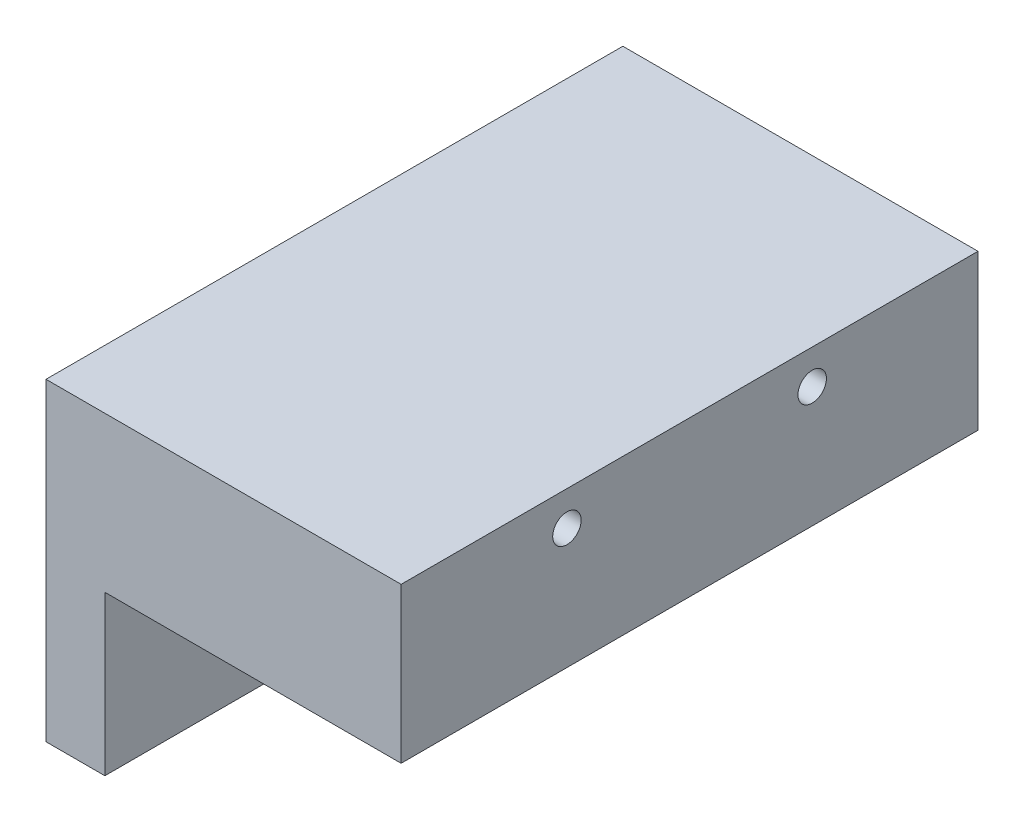
SolidWorks part; units mm, degrees
ref_plane "Front Plane" through (0, 0, 0) normal (1, 0, 0) x (0, 1, 0)
ref_plane "Top Plane" through (0, 0, 0) normal (0, 0, 1) x (0, 1, 0)
ref_plane "Right Plane" through (0, 0, 0) normal (0, 1, 0) x (-1, 0, 0)
sketch "Sketch1" plane through (0, 0, 0) normal (1, 0, 0) x (0, 1, 0)
  line L0 (0.2, 29.4) -> (0.2, -29.4)
  line L1 (-16, -29.4) -> (16, -29.4)
  line L2 (-16, -29.4) -> (-16, 29.4)
  line L3 (-16, 29.4) -> (16, 29.4)
  line L4 (16, -29.4) -> (16, 29.4)
  line L5 (-16, -29.4) -> (16, 29.4) construction
  line L6 (-16, 29.4) -> (16, -29.4) construction
  line L7 (12.5, -12.5) -> (-12.5, -12.5) construction
  line L8 (12.5, -12.5) -> (12.5, 12.5) construction
  line L9 (12.5, 12.5) -> (-12.5, 12.5) construction
  line L10 (-12.5, -12.5) -> (-12.5, 12.5) construction
  line L11 (12.5, -12.5) -> (-12.5, 12.5) construction
  line L12 (12.5, 12.5) -> (-12.5, -12.5) construction
  circle A0 centre (-12.5, 12.5) radius 1.45
  circle A1 centre (12.5, 12.5) radius 1.45
  circle A2 centre (12.5, -12.5) radius 1.45
  circle A3 centre (-12.5, -12.5) radius 1.45
  circle A4 centre (-12.5, 12.5) radius 2.5
  circle A5 centre (-12.5, -12.5) radius 2.5
  circle A6 centre (12.5, 12.5) radius 2.5
  circle A7 centre (12.5, -12.5) radius 2.5
  point P0 (0, 0)
  point P6 (0, 0)
  dimension "D4" = 2.9
  dimension "D6" = 5
  dimension "D1" = 25
  dimension "D2" = 32
  dimension "D3" = 58.8
  dimension "D5" = 0.2
extrude "Boss-Extrude1" add sketch "Sketch1" against normal blind 6 contours L3 L2 L1 L0 A3 A0 | L1 L4 L3 L0 A2 A1 | A4 A0 | A6 A1 | A5 A3 | A7 A2 region at (0, 7.9058, 0) region at (0, -7.7022, 0) region at (0, -14.9293, 12.5) region at (0, -14.9293, -12.5) region at (0, 10.0707, 12.5) region at (0, 10.0707, -12.5)
extrude "Boss-Extrude2" add sketch "Sketch1<3>" along normal blind 30.2 contours L1 L4 L3 L0 A7 A6 | A6 A1 | A7 A2 region at (0, 7.9058, 0) region at (0, 10.0707, 12.5) region at (0, 10.0707, -12.5)
sketch "Sketch1<3>" plane through (0, 0, 0) normal (1, 0, 0) x (0, 1, 0) same geometry as "Sketch1"
sketch "Sketch2" plane through (0, 0.2, 0) normal (0, -1, 0) x (1, 0, 0)
  line L0 (0, 29.4) -> (30.2, 0.6)
  line L1 (30.2, -29.4) -> (0.2, -29.4)
  line L2 (30.2, -29.4) -> (30.2, 0.6)
  line L3 (30.2, 0.6) -> (0.2, 0.6)
  line L4 (0.2, -29.4) -> (0.2, 0.6)
  line L5 (30.2, 29.4) -> (30.2, -29.4) construction
  line L6 (30.2, 29.4) -> (0, 29.4) construction
  line L7 (30.2, 29.4) -> (30.2, -29.4)
  line L8 (30.2, 29.4) -> (0, 29.4)
  line L9 (0.2, 0.6) -> (30.2, -29.4) construction
  circle A0 centre (15.2, -14.4) radius 3.2
  point P10 (0, 0)
  dimension "D2" = 6.4
  dimension "D1" = 30
